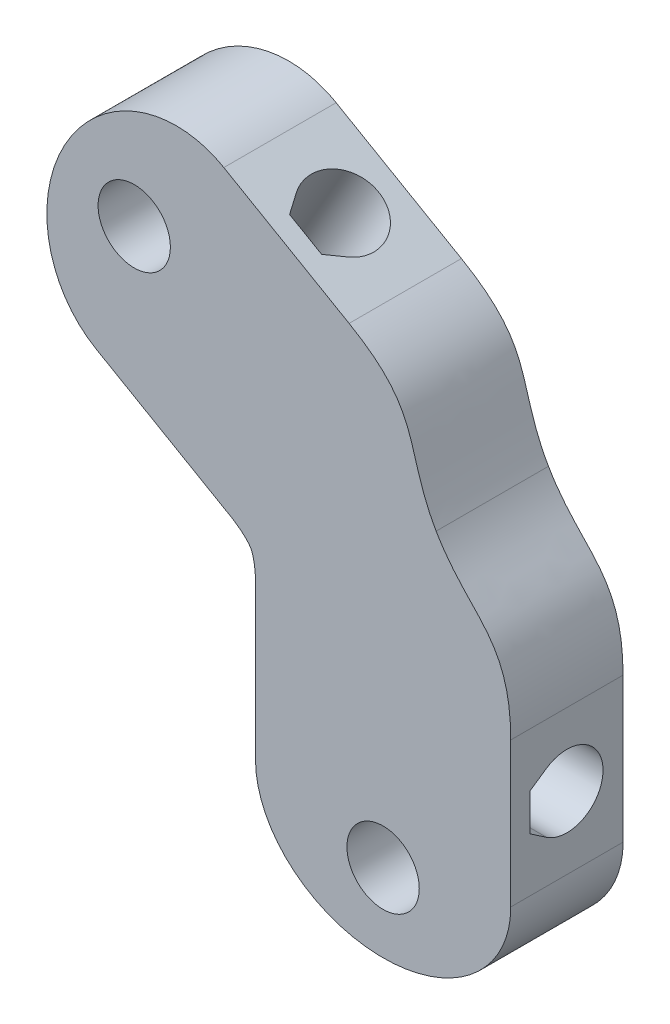
SolidWorks part; units mm, degrees
ref_plane "Piano frontale" through (0, 0, 0) normal (0, 0, 1) x (1, 0, 0)
ref_plane "Piano superiore" through (0, 0, 0) normal (0, 1, 0) x (1, 0, 0)
ref_plane "Piano destro" through (0, 0, 0) normal (1, 0, 0) x (0, 0, -1)
sketch "Schizzo1" plane through (0, 0, 0) normal (0, 0, 1) x (1, 0, 0)
  line L0 (-61.2733, -35.3762) -> (61.2733, 35.3762) construction
  line L1 (-53.5838, 0) -> (53.5838, 0) construction
  line L2 (0, 33.775) -> (0, -33.775) construction
  line L3 (-15, -13.275) -> (-15, -30.275)
  line L4 (15, -13.275) -> (15, -30.275)
  line L5 (-13.132, -13.2311) -> (-10.36, -18.0322) construction
  line L6 (15, -10.7711) -> (15, -22.7789) construction
  line L7 (3.9927, 7.4846) -> (8.4782, -0.2845) construction
  line L8 (-3.9965, 19.6279) -> (-18.7189, 28.1279)
  line L9 (-18.9965, -6.3529) -> (-33.7189, 2.1471)
  circle A0 centre (0, -33.775) radius 4.25
  circle A1 centre (-29.25, 16.8875) radius 4.25
  ellipse E0 centre (0, -30.275) end of major axis (15, -30.275) minor radius 12.681 (-15, -30.275) -> (15, -30.275) ccw
  ellipse E1 centre (-26.2189, 15.1375) end of major axis (-18.7189, 28.1279) minor radius 12.681 (-33.7189, 2.1471) -> (-18.7189, 28.1279) cw
  spline S0 degree 3 poles (-15, -13.275) (-14.8913, -10.9158) (-15.2403, -9.5793) (-15.5782, -8.9941) knots 0 0 0 0 1 1 1 1
  spline S1 degree 3 poles (15, -13.275) (15, -3.028) (10.1064, -3.1045) (6.2355, 3.6001) knots 0 0 0 0 1 1 1 1
  spline S2 degree 3 poles (-3.9965, 19.6279) (4.8777, 14.5044) (2.3646, 10.3046) (6.2355, 3.6001) knots 0 0 0 0 1 1 1 1
  spline S3 degree 3 poles (-18.9965, -6.3529) (-16.899, -7.4384) (-15.9161, -8.4088) (-15.5782, -8.9941) knots 0 0 0 0 1 1 1 1
  point P7 (0, 0)
  point P10 (0, 0)
  point P43 (0, 0)
  dimension "D3" = 8.5
  dimension "D6" = 30
  dimension "D7" = 9.181
  dimension "D1" = 30
  dimension "D2" = 3.5
  dimension "D4" = 29.25
  dimension "D5" = 17
extrude "Estrusione-Estrusione1" add sketch "Schizzo1" along normal mid plane 13.2 contours A1 | S0 S3 L9 E1 L8 S2 S1 L4 E0 L3 | A0 region at (-29.25, 16.8875, 0)
sketch "Schizzo11" plane through (15, 0, 0) normal (1, 0, 0) x (0, 0, -1)
  line L0 (-6.6, -13.275) -> (-6.6, -30.275) construction
  line L1 (6.6, -13.275) -> (6.6, -30.275) construction
  line L2 (-6.6, -13.275) -> (-6.6, -30.275) construction
  line L3 (6.6, -13.275) -> (6.6, -30.275) construction
  line L4 (-6.6, -21.775) -> (6.6, -21.775) construction
  line L5 (-4.35, -23.95) -> (-4.35, -19.6)
  line L6 (-4.35, -19.6) -> (-2.3978, -18.266)
  line L7 (-4.35, -23.95) -> (-2.3978, -25.284)
  arc A0 (-2.3978, -25.284) -> (-2.3978, -18.266) centre (0, -21.775) ccw
  point P11 (-4.35, -21.775)
  dimension "D1" = 8.5
  dimension "D2" = 2.25
  dimension "D3" = 4.35
sketch "Schizzo12" plane through (7.5, 12.9904, 0) normal (0.5, 0.866, 0) x (0.866, -0.5, 0)
  line L0 (-13.275, -6.6) -> (-30.275, -6.6) construction
  line L1 (-13.275, 6.6) -> (-30.275, 6.6) construction
  line L2 (-13.275, -6.6) -> (-30.275, -6.6) construction
  line L3 (-13.275, 6.6) -> (-30.275, 6.6) construction
  line L4 (-21.775, -6.6) -> (-21.775, 6.6) construction
  line L5 (-19.6, -4.35) -> (-23.95, -4.35)
  line L6 (-19.6, -4.35) -> (-18.266, -2.3978)
  line L7 (-23.95, -4.35) -> (-25.284, -2.3978)
  arc A0 (-18.266, -2.3978) -> (-25.284, -2.3978) centre (-21.775, 0) ccw
  point P11 (-21.775, -4.35)
  dimension "D1" = 8.5
  dimension "D2" = 2.25
  dimension "D3" = 4.35
extrude "Taglio-Estrusione1" cut sketch "Schizzo11" against normal up to next contours A0 L6 L5 L7
extrude "Taglio-Estrusione2" cut sketch "Schizzo12" against normal up to next contours A0 L7 L5 L6
